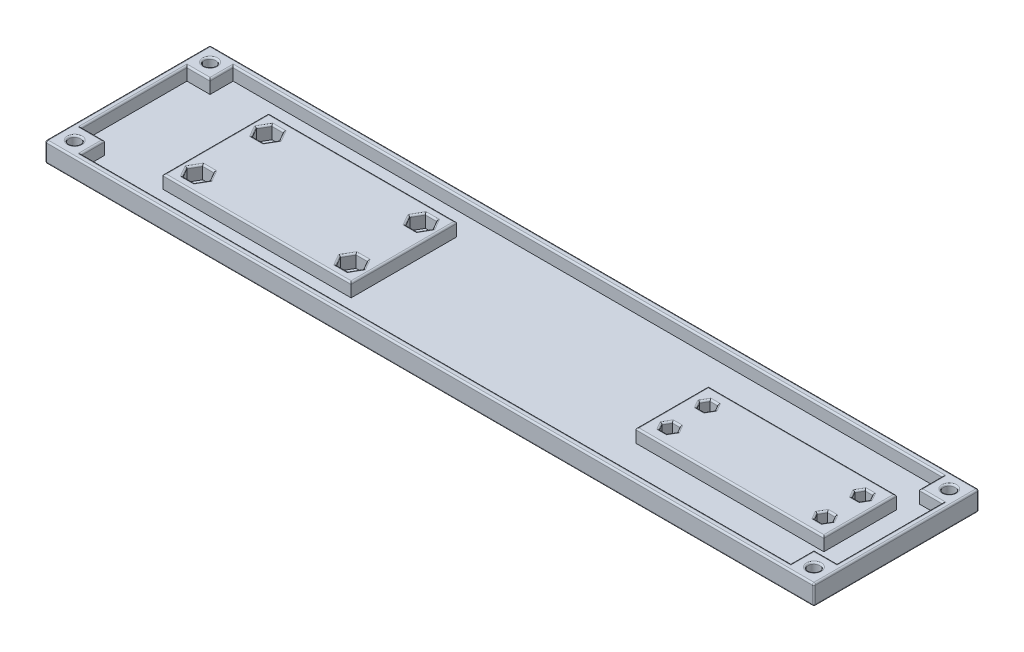
SolidWorks part; units mm, degrees
ref_plane "Front Plane" through (0, 0, 0) normal (0, 0, 1) x (1, 0, 0)
ref_plane "Top Plane" through (0, 0, 0) normal (0, 1, 0) x (1, 0, 0)
ref_plane "Right Plane" through (0, 0, 0) normal (1, 0, 0) x (0, 0, -1)
sketch "Sketch1" plane through (0, 0, -41.3466) normal (0, 1, 0) x (1, 0, 0)
  line L0 (-32, 10.5) -> (-16, 10.5) construction
  line L1 (0, 0) -> (46.5, 0) construction
  line L2 (0, 0) -> (0, 21) construction
  line L3 (0, 21) -> (46.5, 21) construction
  line L4 (46.5, 0) -> (46.5, 21) construction
  line L5 (1.7321, 24) -> (-1.7321, 24)
  line L6 (-1.7321, 24) -> (-3.4641, 21)
  line L7 (-3.4641, 21) -> (-1.7321, 18)
  line L8 (-1.7321, 18) -> (1.7321, 18)
  line L9 (1.7321, 18) -> (3.4641, 21)
  line L10 (3.4641, 21) -> (1.7321, 24)
  line L11 (43.0359, 21) -> (44.7679, 18)
  line L12 (44.7679, 18) -> (48.2321, 18)
  line L13 (48.2321, 18) -> (49.9641, 21)
  line L14 (49.9641, 21) -> (48.2321, 24)
  line L15 (48.2321, 24) -> (44.7679, 24)
  line L16 (44.7679, 24) -> (43.0359, 21)
  line L17 (43.0359, 0) -> (44.7679, -3)
  line L18 (44.7679, -3) -> (48.2321, -3)
  line L19 (48.2321, -3) -> (49.9641, 0)
  line L20 (49.9641, 0) -> (48.2321, 3)
  line L21 (48.2321, 3) -> (44.7679, 3)
  line L22 (44.7679, 3) -> (43.0359, 0)
  line L23 (3.4641, 0) -> (1.7321, 3)
  line L24 (1.7321, 3) -> (-1.7321, 3)
  line L25 (-1.7321, 3) -> (-3.4641, 0)
  line L26 (-3.4641, 0) -> (-1.7321, -3)
  line L27 (-1.7321, -3) -> (1.7321, -3)
  line L28 (1.7321, -3) -> (3.4641, 0)
  line L33 (201, 10.5) -> (185, 10.5) construction
  line L34 (185, 16.2) -> (185, 10.5) construction
  line L35 (185, 4.8) -> (138, 4.8) construction
  line L36 (-32, 10.5) -> (-32, 35.5)
  line L37 (-32, 35.5) -> (84.5, 35.5)
  line L38 (84.5, 35.5) -> (201, 35.5)
  line L39 (201, 35.5) -> (201, 10.5)
  line L40 (201, 10.5) -> (201, -14.5)
  line L41 (201, -14.5) -> (84.5, -14.5)
  line L42 (84.5, -14.5) -> (-32, -14.5)
  line L43 (-32, -14.5) -> (-32, 10.5)
  line L44 (-27.5, 31) -> (84.5, 31) construction
  line L45 (84.5, 31) -> (196.5, 31) construction
  line L46 (196.5, 31) -> (196.5, 10.5) construction
  line L47 (196.5, 10.5) -> (196.5, -10) construction
  line L48 (196.5, -10) -> (84.5, -10) construction
  line L49 (84.5, -10) -> (-27.5, -10) construction
  line L50 (-27.5, -10) -> (-27.5, 10.5) construction
  line L51 (-27.5, 10.5) -> (-27.5, 31) construction
  line L52 (138, 4.8) -> (138, 16.2) construction
  line L53 (138, 16.2) -> (185, 16.2) construction
  line L54 (185, 10.5) -> (185, 4.8) construction
  line L55 (0, 10.5) -> (-16, 10.5) construction
  line L56 (135.6906, 16.2) -> (136.8453, 14.2)
  line L57 (136.8453, 14.2) -> (139.1547, 14.2)
  line L58 (139.1547, 14.2) -> (140.3094, 16.2)
  line L59 (140.3094, 16.2) -> (139.1547, 18.2)
  line L60 (139.1547, 18.2) -> (136.8453, 18.2)
  line L61 (136.8453, 18.2) -> (135.6906, 16.2)
  line L62 (182.6906, 16.2) -> (183.8453, 14.2)
  line L63 (183.8453, 14.2) -> (186.1547, 14.2)
  line L64 (186.1547, 14.2) -> (187.3094, 16.2)
  line L65 (187.3094, 16.2) -> (186.1547, 18.2)
  line L66 (186.1547, 18.2) -> (183.8453, 18.2)
  line L67 (183.8453, 18.2) -> (182.6906, 16.2)
  line L68 (182.6906, 4.8) -> (183.8453, 2.8)
  line L69 (183.8453, 2.8) -> (186.1547, 2.8)
  line L70 (186.1547, 2.8) -> (187.3094, 4.8)
  line L71 (187.3094, 4.8) -> (186.1547, 6.8)
  line L72 (186.1547, 6.8) -> (183.8453, 6.8)
  line L73 (183.8453, 6.8) -> (182.6906, 4.8)
  line L74 (140.3094, 4.8) -> (139.1547, 6.8)
  line L75 (139.1547, 6.8) -> (136.8453, 6.8)
  line L76 (136.8453, 6.8) -> (135.6906, 4.8)
  line L77 (135.6906, 4.8) -> (136.8453, 2.8)
  line L78 (136.8453, 2.8) -> (139.1547, 2.8)
  line L79 (139.1547, 2.8) -> (140.3094, 4.8)
  line L80 (0, 10.5) -> (46.5, 10.5) construction
  line L81 (51.75, -5.5) -> (-5.25, -5.5)
  line L82 (51.75, -5.5) -> (51.75, 26.5)
  line L83 (51.75, 26.5) -> (-5.25, 26.5)
  line L84 (-5.25, -5.5) -> (-5.25, 26.5)
  line L85 (51.75, -5.5) -> (-5.25, 26.5) construction
  line L86 (51.75, 26.5) -> (-5.25, -5.5) construction
  line L87 (161.5, 4.8) -> (161.5, 16.2) construction
  line L89 (190, -0.5) -> (133, -0.5)
  line L90 (190, -0.5) -> (190, 21.5)
  line L91 (190, 21.5) -> (133, 21.5)
  line L92 (133, -0.5) -> (133, 21.5)
  line L93 (190, -0.5) -> (133, 21.5) construction
  line L94 (190, 21.5) -> (133, -0.5) construction
  line L95 (-23, 26.5) -> (-32, 26.5)
  line L96 (-23, 26.5) -> (-23, 35.5)
  line L97 (-23, 35.5) -> (-32, 35.5)
  line L98 (-32, 26.5) -> (-32, 35.5)
  line L99 (-23, 26.5) -> (-32, 35.5) construction
  line L100 (-23, 35.5) -> (-32, 26.5) construction
  line L101 (-23, -5.5) -> (-32, -5.5)
  line L102 (-23, -5.5) -> (-23, -14.5)
  line L103 (-23, -14.5) -> (-32, -14.5)
  line L104 (-32, -5.5) -> (-32, -14.5)
  line L105 (-23, -5.5) -> (-32, -14.5) construction
  line L106 (-23, -14.5) -> (-32, -5.5) construction
  line L107 (192, -5.5) -> (201, -5.5)
  line L108 (192, -5.5) -> (192, -14.5)
  line L109 (192, -14.5) -> (201, -14.5)
  line L110 (201, -5.5) -> (201, -14.5)
  line L111 (192, -5.5) -> (201, -14.5) construction
  line L112 (192, -14.5) -> (201, -5.5) construction
  line L113 (192, 26.5) -> (201, 26.5)
  line L114 (192, 26.5) -> (192, 35.5)
  line L115 (192, 35.5) -> (201, 35.5)
  line L116 (201, 26.5) -> (201, 35.5)
  line L117 (192, 26.5) -> (201, 35.5) construction
  line L118 (192, 35.5) -> (201, 26.5) construction
  line L119 (84.5, 33.5) -> (192, 33.5)
  line L121 (199, 10.5) -> (199, -5.5)
  line L122 (192, -12.5) -> (84.5, -12.5)
  line L123 (84.5, -12.5) -> (-23, -12.5)
  line L125 (-30, 10.5) -> (-30, 26.5)
  line L126 (-23, 33.5) -> (84.5, 33.5)
  line L127 (-30, 33.5) -> (84.5, 33.5) construction
  line L128 (-30, 10.5) -> (-30, 33.5) construction
  line L129 (-30, -5.5) -> (-30, 10.5)
  line L130 (-30, -12.5) -> (-30, 10.5) construction
  line L131 (84.5, -12.5) -> (-30, -12.5) construction
  line L132 (199, -12.5) -> (84.5, -12.5) construction
  line L133 (199, 10.5) -> (199, -12.5) construction
  line L134 (199, 26.5) -> (199, 10.5)
  line L135 (199, 33.5) -> (199, 10.5) construction
  line L136 (84.5, 33.5) -> (199, 33.5) construction
  circle A0 centre (46.5, 21) radius 1.75
  circle A1 centre (46.5, 0) radius 1.75
  circle A2 centre (0, 0) radius 1.75
  circle A3 centre (0, 21) radius 1.75
  circle A4 centre (0, 21) radius 3 construction
  circle A5 centre (46.5, 21) radius 3 construction
  circle A6 centre (46.5, 0) radius 3 construction
  circle A7 centre (0, 0) radius 3 construction
  circle A8 centre (-27.5, 31) radius 1.75
  circle A9 centre (196.5, 31) radius 1.75
  circle A10 centre (196.5, -10) radius 1.75
  circle A11 centre (-27.5, -10) radius 1.75
  circle A12 centre (138, 16.2) radius 2 construction
  circle A13 centre (185, 16.2) radius 2 construction
  circle A14 centre (185, 4.8) radius 2 construction
  circle A15 centre (138, 4.8) radius 2 construction
  circle A16 centre (138, 16.2) radius 1.25
  circle A17 centre (138, 4.8) radius 1.25
  circle A18 centre (185, 4.8) radius 1.25
  circle A19 centre (185, 16.2) radius 1.25
  point P45 (23.25, 10.5)
  point P104 (161.5, 10.5)
  dimension "D3" = 3.5
  dimension "D4" = 6
  dimension "D8" = 4
  dimension "D12" = 2.5
  dimension "D1" = 46.5
  dimension "D2" = 21
  dimension "D5" = 116.5
  dimension "D6" = 25
  dimension "D9" = 11.4
  dimension "D10" = 47
  dimension "D11" = 16
  dimension "D13" = 16
  dimension "D14" = 57
  dimension "D15" = 57
  dimension "D16" = 22
  dimension "D17" = 32
  dimension "D7" = 4.5
  dimension "D18" = 2
extrude "Boss-Extrude1" add sketch "Sketch1" along normal blind 4 contours L92 L89 L90 L91 L61 L60 L59 L58 L57 L56 L67 L66 L65 L64 L63 L62 L73 L72 L71 L70 L69 L68 L79 L78 L77 L76 L75 L74 | L84 L81 L82 L83 L28 L27 L26 L25 L24 L23 L22 L21 L20 L19 L18 L17 L16 L15 L14 L13 L12 L11 L10 L9 L8 L7 L6 L5 | L122 L123 L102 L42 L41 L108 | L96 L126 L119 L114 L38 L37 | L101 L129 L125 L95 L36 L43 | L95 L96 L37 L36 A8 | L102 L101 L43 L42 A11 | L107 L108 L41 L40 A10 | L114 L113 L39 L38 A9 | L113 L134 L121 L107 L40 L39 region at (-31, 0, -51.8466) region at (-31.8727, 0, -72.3466) region at (-31, 0, -35.7193) region at (84.5, 0, -75.8466) region at (84.5, 0, -27.8466) region at (196.5, 0, -76.7193) region at (192.1273, 0, -27.8466) region at (200, 0, -51.8466) region at (23.25, 0, -51.8466) region at (161.5, 0, -51.8466)
extrude "Boss-Extrude2" add sketch "Sketch1<3>" against normal blind 2 contours L113 L114 L38 L37 L96 L95 L36 L43 L101 L102 L42 L41 L108 L107 L40 L90 L89 L92 L91 L39 L81 L84 L83 L82 | L114 L113 L39 L38 A9 | L107 L108 L41 L40 A10 | L102 L101 L43 L42 A11 | L95 L96 L37 L36 A8 | L84 L81 L82 L83 L28 L27 L26 L25 L24 L23 L22 L21 L20 L19 L18 L17 L16 L15 L14 L13 L12 L11 L10 L9 L8 L7 L6 L5 | L92 L89 L90 L91 L61 L60 L59 L58 L57 L56 L67 L66 L65 L64 L63 L62 L73 L72 L71 L70 L69 L68 L79 L78 L77 L76 L75 L74 | L60 L61 L56 L57 L58 L59 A16 | L72 L73 L68 L69 L70 L71 A18 | L66 L67 L62 L63 L64 L65 A19 | L21 L22 L17 L18 L19 L20 A1 | L15 L16 L11 L12 L13 L14 A0 | L9 L10 L5 L6 L7 L8 A3 | L27 L28 L23 L24 L25 L26 A2 | L78 L79 L74 L75 L76 L77 A17 | L122 L123 L102 L42 L41 L108 | L96 L126 L119 L114 L38 L37 | L113 L134 L121 L107 L40 L39 | L101 L129 L125 L95 L36 L43 region at (2.5187, 0, -63.8008) region at (43.9813, 0, -63.8008) region at (43.9813, 0, -42.8008) region at (2.5187, 0, -39.8924) region at (-31, 0, -51.8466) region at (-31.8727, 0, -72.3466) region at (-31, 0, -35.7193) region at (86.5884, 0, -51.8466) region at (84.5, 0, -75.8466) region at (84.5, 0, -27.8466) region at (196.5, 0, -76.7193) region at (192.1273, 0, -27.8466) region at (200, 0, -51.8466) region at (136.3209, 0, -58.516) region at (183.3209, 0, -58.516) region at (183.3209, 0, -47.116) region at (139.6791, 0, -45.1772) region at (23.25, 0, -51.8466) region at (161.5, 0, -51.8466)
sketch "Sketch1<3>" plane through (0, 0, -41.3466) normal (0, 1, 0) x (1, 0, 0) same geometry as "Sketch1"
fillet "Fillet1" radius 0.5 84 edges at (-32, 1, -76.8466) (201, 1, -26.8466) (-32, 1, -26.8466) (84.5, 4, -26.8466) (201, 4, -51.8466) (-32, 4, -51.8466) (195.5, 4, -67.8466) (192, 4, -71.3466) (196.5, 4, -70.5966) (192, 4, -32.3466) (195.5, 4, -35.8466) (196.5, 4, -29.5966) (-26.5, 4, -35.8466) (-23, 4, -32.3466) (-27.5, 4, -29.5966) (-23, 4, -71.3466) (-26.5, 4, -67.8466) (-27.5, 4, -70.5966) (139.7321, 4, -47.1466) (138, 4, -48.1466) (136.2679, 4, -47.1466) (136.2679, 4, -45.1466) (138, 4, -44.1466) (139.7321, 4, -45.1466) (183.2679, 4, -45.1466) (185, 4, -44.1466) (186.7321, 4, -45.1466) (186.7321, 4, -47.1466) (185, 4, -48.1466) (183.2679, 4, -47.1466) (183.2679, 4, -56.5466) (185, 4, -55.5466) (186.7321, 4, -56.5466) (186.7321, 4, -58.5466) (185, 4, -59.5466) (183.2679, 4, -58.5466) (136.2679, 4, -56.5466) (138, 4, -55.5466) (139.7321, 4, -56.5466) (139.7321, 4, -58.5466) (138, 4, -59.5466) (136.2679, 4, -58.5466) (161.5, 4, -62.8466) (190, 4, -51.8466) (161.5, 4, -40.8466) (133, 4, -51.8466) (0, 4, -65.3466) (-2.5981, 4, -63.8466) (-2.5981, 4, -60.8466) (0, 4, -59.3466) (2.5981, 4, -60.8466) (2.5981, 4, -63.8466) (43.9019, 4, -60.8466) (46.5, 4, -59.3466) (49.0981, 4, -60.8466) (49.0981, 4, -63.8466) (46.5, 4, -65.3466) (43.9019, 4, -63.8466) (43.9019, 4, -39.8466) (46.5, 4, -38.3466) (49.0981, 4, -39.8466) (49.0981, 4, -42.8466) (46.5, 4, -44.3466) (43.9019, 4, -42.8466) (2.5981, 4, -42.8466) (0, 4, -44.3466) (-2.5981, 4, -42.8466) (-2.5981, 4, -39.8466) (0, 4, -38.3466) (2.5981, 4, -39.8466) (23.25, 4, -67.8466) (51.75, 4, -51.8466) (23.25, 4, -35.8466) (-5.25, 4, -51.8466) (201, 1, -76.8466) (199, 4, -51.8466) (84.5, 4, -74.8466) (-30, 4, -51.8466) (84.5, 4, -28.8466) (84.5, 4, -76.8466) (201, -2, -51.8466) (84.5, -2, -76.8466) (-32, -2, -51.8466) (84.5, -2, -26.8466)
